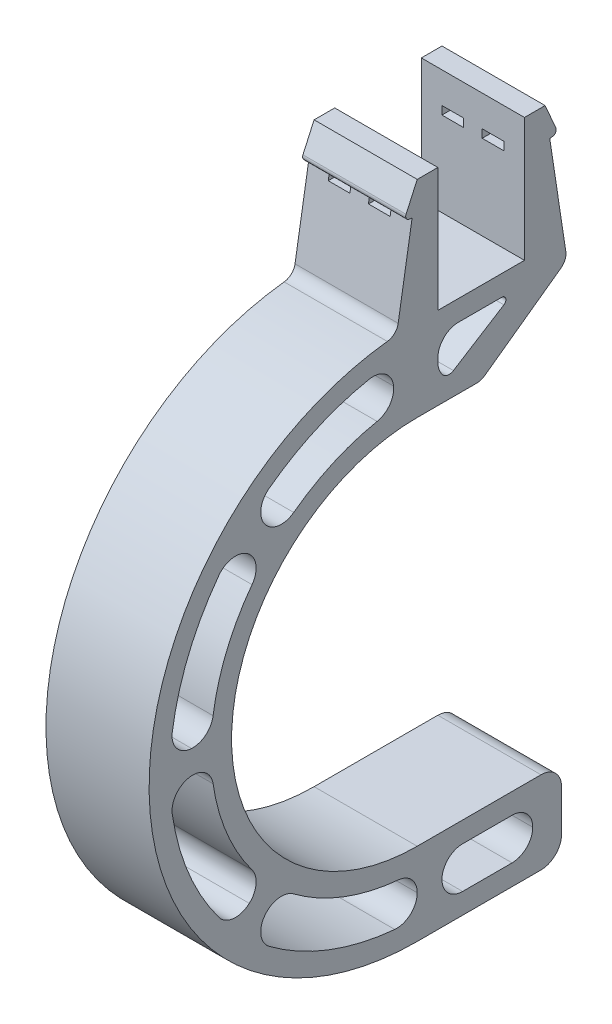
SolidWorks part; units mm, degrees
ref_plane "Front Plane" through (0, 0, 0) normal (0, 0, 1) x (1, 0, 0)
ref_plane "Top Plane" through (0, 0, 0) normal (0, 1, 0) x (1, 0, 0)
ref_plane "Right Plane" through (0, 0, 0) normal (1, 0, 0) x (0, 0, -1)
sketch "Sketch1" plane through (0, 0, 0) normal (1, 0, 0) x (0, 0, -1)
  line L0 (-10.5, 2.5) -> (-10.5, 32.5)
  line L1 (-10.5, 2.5) -> (10.5, 2.5)
  line L2 (-15.5, -17.5) -> (0, -17.5)
  line L3 (0, -17.5) -> (20.8, -2.5)
  line L4 (-10.5, -12.7739) -> (-10.5, -2.5)
  line L5 (-15.5, 32.5) -> (-20.5, 2.3074)
  line L6 (-15.5, -112.5) -> (-15.5, -122.5)
  line L7 (-10.5, -2.5) -> (8.4637, -2.5)
  line L8 (8.4637, -2.5) -> (-7.9175, -12.7739)
  line L9 (-15.5, 32.5) -> (-10.5, 32.5)
  line L10 (15.5, 32.5) -> (20.8, -2.5)
  line L11 (-7.9175, -12.7739) -> (-10.5, -12.7739)
  line L12 (-65.4315, -65.1168) -> (-75.4178, -65.6402)
  line L13 (15.5, 32.5) -> (10.5, 32.5)
  line L14 (-65.4315, -59.8832) -> (-75.4178, -59.3598)
  line L15 (10.5, 2.5) -> (10.5, 32.5)
  line L16 (-52.6572, -29.0435) -> (-60.0887, -22.3522)
  line L17 (-15.5, -127.5) -> (19.5, -127.5)
  line L18 (-15.5, -122.5) -> (-15.5, -112.5)
  line L19 (-15.5, -107.5) -> (19.5, -107.5)
  line L20 (19.5, -127.5) -> (19.5, -107.5)
  line L21 (-48.9565, -25.3428) -> (-55.6478, -17.9113)
  line L22 (-20.7264, -12.7739) -> (-21.7717, -2.8287)
  line L23 (-52.6572, -95.9565) -> (-60.0887, -102.6478)
  line L24 (-48.9565, -99.6572) -> (-55.6478, -107.0887)
  line L26 (-9.5, -112.5) -> (12.5, -112.5)
  line L27 (-9.5, -112.5) -> (-9.5, -122.5)
  line L28 (-9.5, -122.5) -> (12.5, -122.5)
  line L29 (12.5, -112.5) -> (12.5, -122.5)
  arc A0 (-20.5, 2.3074) -> (-15.5, -127.5) centre (-15.5, -62.5) ccw
  arc A1 (-15.5, -17.5) -> (-15.5, -107.5) centre (-15.5, -62.5) ccw
  arc A2 (-20.7264, -12.7739) -> (-48.9565, -25.3428) centre (-15.5, -62.5) ccw
  arc A3 (-21.7717, -2.8287) -> (-55.6478, -17.9113) centre (-15.5, -62.5) ccw
  arc A4 (-52.6572, -29.0435) -> (-65.4315, -59.8832) centre (-15.5, -62.5) ccw
  arc A5 (-60.0887, -22.3522) -> (-75.4178, -59.3598) centre (-15.5, -62.5) ccw
  arc A6 (-48.9565, -99.6572) -> (-15.5, -112.5) centre (-15.5, -62.5) ccw
  arc A7 (-55.6478, -107.0887) -> (-15.5, -122.5) centre (-15.5, -62.5) ccw
  arc A8 (-75.4178, -65.6402) -> (-60.0887, -102.6478) centre (-15.5, -62.5) ccw
  arc A9 (-65.4315, -65.1168) -> (-52.6572, -95.9565) centre (-15.5, -62.5) ccw
  point P0 (0, 0)
  dimension "D7" = 130
  dimension "D9" = 20
  dimension "D5" = 5
  dimension "D6" = 5
  dimension "D2" = 21
  dimension "D3" = 5
  dimension "D4" = 5
  dimension "D8" = 65
  dimension "D10" = 6
  dimension "D11" = 7
  dimension "D12" = 35
extrude "Boss-Extrude1" add sketch "Sketch1" against normal blind 25 contours A1 L2 L3 L10 L13 L15 L1 L0 L9 L5 A0 L17 L20 L19 A7 L24 A6 L6 A5 L16 A4 L14 A3 L22 A2 L21 L8 L11 L4 L7 L26 L29 L28 L27 L12 A9 L23 A8 region at (0, 0.6063, 0)
fillet "Fillet1" radius 5 18 edges at (-12.5, -99.6572, 48.9565) (-12.5, -112.5, 9.5) (-12.5, -122.5, 9.5) (-12.5, -122.5, 15.5) (-12.5, -122.5, -12.5) (-12.5, -112.5, -12.5) (-12.5, -107.0887, 55.6478) (-12.5, -112.5, 15.5) (-12.5, -95.9565, 52.6572) (-12.5, -102.6478, 60.0887) (-12.5, -22.3522, 60.0887) (-12.5, -29.0435, 52.6572) (-12.5, -59.8832, 65.4315) (-12.5, -59.3598, 75.4178) (-12.5, -17.9113, 55.6478) (-12.5, -25.3428, 48.9565) (-12.5, -12.7739, 20.7264) (-12.5, -2.8287, 21.7717)
fillet "Fillet2" radius 5 2 edges at (-12.5, -65.1168, 65.4315) (-12.5, -65.6402, 75.4178)
fillet "Fillet3" radius 5 1 edges at (-12.5, -2.5, 10.5)
fillet "Fillet4" radius 5 1 edges at (-12.5, -12.7739, 10.5)
fillet "Fillet5" radius 2 1 edges at (-12.5, -12.7739, 7.9175)
fillet "Fillet6" radius 1 1 edges at (-12.5, -2.5, -8.4637)
fillet "Fillet7" radius 3 3 edges at (-12.5, -17.5, 0) (-12.5, -2.5, -20.8) (-12.5, 2.3074, 20.5)
fillet "Fillet8" radius 5 2 edges at (-12.5, -127.5, -19.5) (-12.5, -107.5, -19.5)
sketch "Sketch2" plane through (0, 0, -10.5) normal (0, 0, 1) x (1, 0, 0)
  line L0 (-25, 2.5) -> (0, 2.5) construction
  line L1 (-20, 25) -> (-14.75, 25)
  line L2 (-20, 25) -> (-20, 23)
  line L3 (-20, 23) -> (-14.75, 23)
  line L4 (-5, 25) -> (-5, 23)
  line L5 (-20, 25) -> (-14.75, 24.3) construction
  line L6 (-20, 23) -> (-14.75, 23.7) construction
  line L7 (0, 2.5) -> (0, 32.5) construction
  line L8 (-10.25, 25) -> (-5, 25)
  line L10 (-14.75, 23) -> (-14.75, 25)
  line L12 (-10.25, 23) -> (-10.25, 25)
  line L15 (-10.25, 24.3) -> (-5, 25) construction
  line L16 (-10.25, 23.7) -> (-5, 23) construction
  line L17 (-10.25, 23) -> (-5, 23)
  point P0 (-12.5, 24)
  point P9 (-12.5, 24)
  dimension "D1" = 20.5
  dimension "D2" = 15
  dimension "D3" = 5
  dimension "D4" = 2
  dimension "D5" = 4.5
extrude "Cut-Extrude1" cut sketch "Sketch2" against normal blind 25 and the other way blind 35
sketch "Sketch3" plane through (0, 0, 0) normal (1, 0, 0) x (0, 0, -1)
  line L0 (16.6357, 25) -> (18.6357, 25.3029)
  line L1 (15.5, 32.5) -> (20.5258, -0.689) construction
  line L2 (18.6357, 25.3029) -> (15.5, 32.5)
  line L3 (15.5, 32.5) -> (16.6357, 25)
  line L4 (-16.742, 25) -> (-18.742, 25.3312)
  line L5 (-15.5, 32.5) -> (-20.1227, 4.5858) construction
  line L6 (-18.742, 25.3312) -> (-15.5, 32.5)
  line L7 (-15.5, 32.5) -> (-16.742, 25)
  line L8 (15.5, 32.5) -> (10.5, 32.5) construction
  line L9 (-15.5, 32.5) -> (-10.5, 32.5) construction
  dimension "D1" = 2
  dimension "D2" = 2
  dimension "D3" = 7.5
  dimension "D4" = 7.5
extrude "Boss-Extrude2" add sketch "Sketch3" against normal blind 25
fillet "Fillet9" radius 1 2 edges at (-12.5, 25.3029, -18.6357) (-12.5, 25.3312, 18.742)
